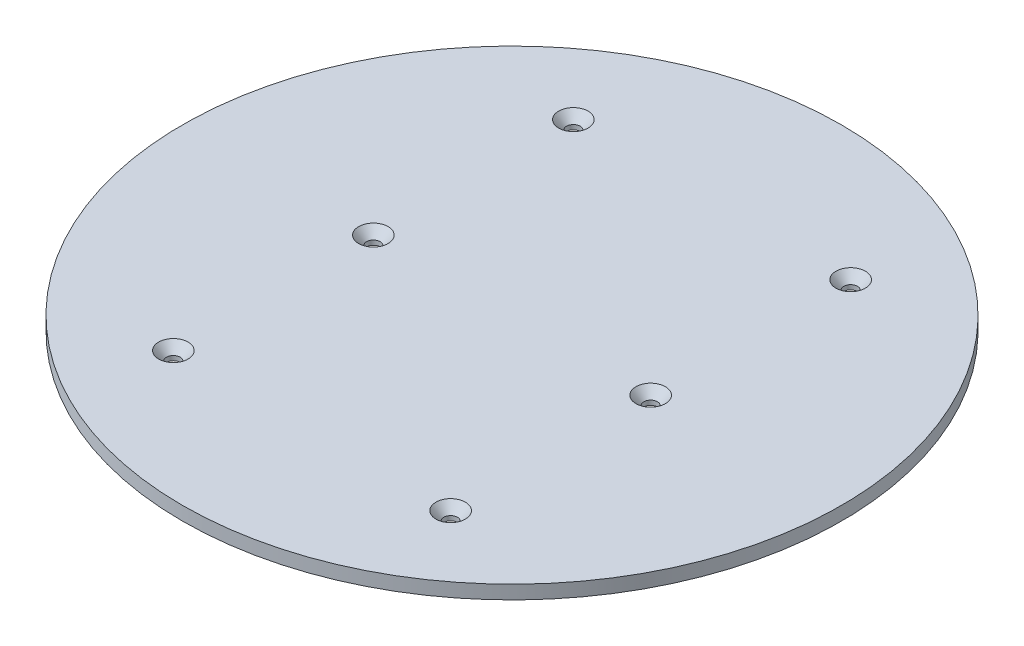
SolidWorks part; units mm, degrees
material "ABS"
ref_plane "Front Plane" through (0, 0, 0) normal (0, 0, 1) x (1, 0, 0)
ref_plane "Top Plane" through (0, 0, 0) normal (0, 1, 0) x (1, 0, 0)
ref_plane "Right Plane" through (0, 0, 0) normal (1, 0, 0) x (0, 0, -1)
sketch "Sketch1" plane through (0, 0, 0) normal (0, 1, 0) x (1, 0, 0)
  circle A0 centre (0, 0) radius 72.5
  dimension "D1" = 145
extrude "Boss-Extrude1" add sketch "Sketch1" along normal blind 3
sketch "Sketch2" plane through (0, 3, 0) normal (0, 1, 0) x (1, 0, 0)
  line L1 (-30.5, -44) -> (30.5, -44) construction
  line L2 (-30.5, -44) -> (-30.5, 44) construction
  line L3 (-30.5, 44) -> (30.5, 44) construction
  line L4 (30.5, -44) -> (30.5, 44) construction
  line L5 (-30.5, -44) -> (30.5, 44) construction
  line L6 (-30.5, 44) -> (30.5, -44) construction
  circle A0 centre (-30.5, 44) radius 1.5
  circle A1 centre (30.5, 44) radius 1.5
  circle A2 centre (30.5, 0) radius 1.5
  circle A3 centre (30.5, -44) radius 1.5
  circle A4 centre (-30.5, -44) radius 1.5
  circle A5 centre (-30.5, 0) radius 1.5
  point P0 (0, 0)
  dimension "D3" = 3
  dimension "D1" = 61
  dimension "D2" = 88
extrude "Cut-Extrude1" cut sketch "Sketch2" against normal through all
chamfer "Chamfer1" distance 2 angle 41 6 edges at (30.5, 3, -42.5) (30.5, 3, 1.5) (30.5, 3, 45.5) (-30.5, 3, 45.5) (-30.5, 3, 1.5) (-30.5, 3, -42.5) first distance on face at (30.5, 0, -42.5) first distance on face at (30.5, 0, 1.5) first distance on face at (30.5, 0, 45.5) first distance on face at (-30.5, 0, 45.5) first distance on face at (-30.5, 0, 1.5) first distance on face at (-30.5, 0, -42.5)
equation "\"smallPulleyTeeth\"= 30"
equation "\"largePulleyTeeth\"= 30"
equation "\"eighthThick\"= 3.0mm"
equation "\"sixteenthThick\" = 1.7mm"
equation "\"quarterThick\"=6.0mm"
equation "\"OD\" = 145mm"
equation "\"puckAngle\" = 60.5deg"
equation "\"puckDiam\" = 76.5mm"
equation "\"puckDist\" = 85mm"
equation "\"scoopFillet\" = 5mm"
equation "\"axlePress\" = 5.9mm"
equation "\"press\" = 0.2mm"
equation "\"wheelClear\" = 0.3mm"
equation "\"10-32clear\" = 4.8mm"
equation "\"10-32tap\" = 4.45mm"
equation "\"6-32clear\" = 3.3mm"
equation "\"8-32clear\" = 4.0mm"
equation "\"4-40clear\" = 3.0mm"
equation "\"wheelHeight\" = 22mm"
equation "\"wheelWell\" = 65mm"
equation "\"ledSmall\" = 3.1mm"
equation "\"ledLarge\" = 4.2mm"
equation "\"ledLength\" = 4.2mm"
equation "\"D1@Sketch1\"=\"OD\""
equation "\"D1@Boss-Extrude1\"=\"eighthThick\""
equation "\"D3@Sketch2\"=\"4-40clear\""
